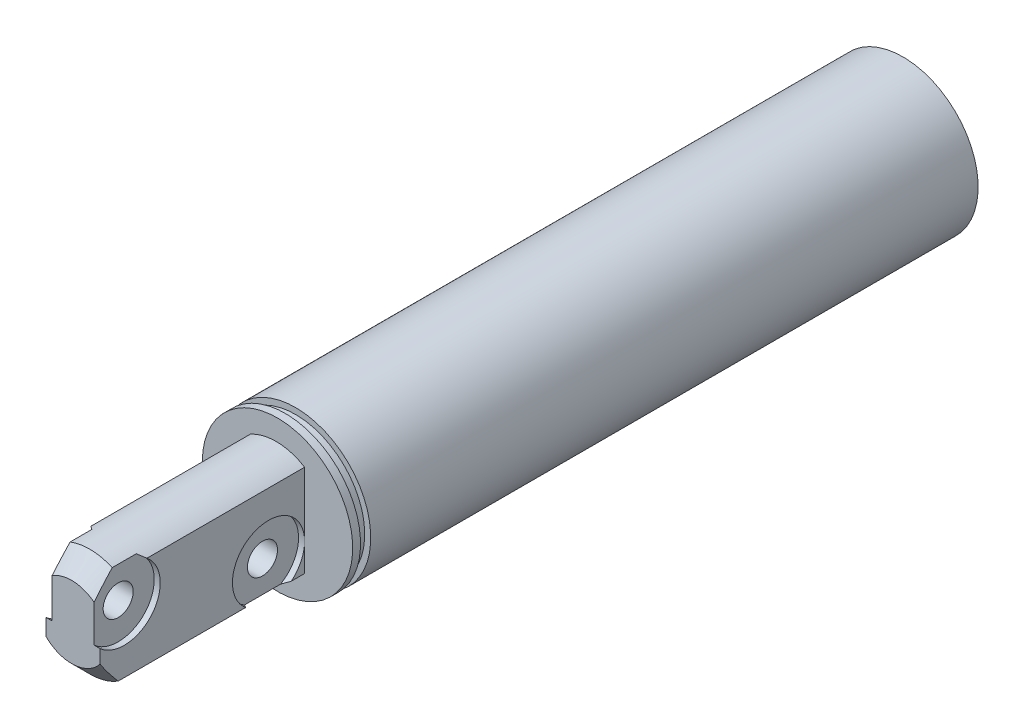
SolidWorks part; units mm, degrees
material "1060 合金"
ref_plane "前视基准面" through (0, 0, 0) normal (0, 0, 1) x (1, 0, 0)
ref_plane "上视基准面" through (0, 0, 0) normal (0, 1, 0) x (1, 0, 0)
ref_plane "右视基准面" through (0, 0, 0) normal (1, 0, 0) x (0, 0, -1)
sketch "草图1" plane through (0, 0, 0) normal (0, 0, 1) x (1, 0, 0)
  circle A0 centre (0, 0) radius 12.5
  dimension "D1" = 25
extrude "凸台-拉伸1" add sketch "草图1" along normal blind 104
sketch "草图6" plane through (0, 0, 0) normal (0, 1, 0) x (1, 0, 0)
  line L0 (0, 0) -> (0, -36.1312) construction
  line L1 (-12.5, 0) -> (-12.5, -104) construction
  line L2 (-12.5, -102.7) -> (-11.5, -102.7)
  line L3 (-12.5, -102.7) -> (-12.5, -101)
  line L4 (-12.5, -101) -> (-11.5, -101)
  line L5 (-11.5, -102.7) -> (-11.5, -101)
  line L6 (12.5, 0) -> (-12.5, 0) construction
  dimension "D1" = 1.7
  dimension "D2" = 101
  dimension "D3" = 1
revolve "切除-旋转1" cut sketch "草图6" angle 360 about L0
sketch "草图7" plane through (0, 0, 0) normal (0, 0, -1) x (-1, 0, 0)
  circle A0 centre (0, 0) radius 8
  circle A1 centre (0, 0) radius 12.5 construction
  dimension "D1" = 16
extrude "凸台-拉伸2" add sketch "草图7" along normal blind 2
hole_wizard "M8 螺纹孔1" positions "草图4" profile "草图5" tap size "M8" standard "GB"
sketch "草图4" plane through (0, 0, -2) normal (0, 0, -1) x (-1, 0, 0)
  point P0 (0, 0)
sketch "草图5" plane through (0, 0, -2) normal (1, 0, 0) x (0, 1, 0)
  line L0 (0, 0) -> (0, 84.2929)
  line L1 (0, 84.2929) -> (3.4, 82.25)
  line L2 (3.4, 82.25) -> (3.4, 0)
  line L5 (3.4, 0) -> (0, 0)
  line L10 (0, 84.2929) -> (-3.4, 82.25) construction
  line L11 (0, -6.35) -> (0, 107.95) construction
  dimension "螺纹孔钻头直径" = 6.8
  dimension "螺纹孔钻头深度" = 82.25
  dimension "导头角度" = 118
cosmetic thread "孔螺蚊线1" parameters "D1"=26, "D2"=8
sketch "草图9" plane through (0, 0, 104) normal (0, 0, 1) x (1, 0, 0)
  circle A0 centre (-0.2311, 0) radius 9
  dimension "D1" = 18
extrude "凸台-拉伸3" add sketch "草图9" along normal blind 34
sketch "草图8" plane through (0, 0, 0) normal (0, 1, 0) x (0, 0, -1)
  line L0 (0, 0) -> (-145.8395, 0) construction
  line L3 (-104, -14.9439) -> (-138, -4.5) construction
  line L4 (-104, 4.5) -> (-138, 4.5)
  line L5 (-104, 4.5) -> (-104, 14.9439)
  line L6 (-104, 14.9439) -> (-138, 14.9439)
  line L7 (-138, 4.5) -> (-138, 14.9439)
  line L8 (-104, 4.5) -> (-138, 14.9439) construction
  line L9 (-104, 14.9439) -> (-138, 4.5) construction
  line L11 (-104, -4.5) -> (-138, -14.9439) construction
  line L12 (-138, -4.5) -> (-138, -14.9439)
  line L13 (-104, -14.9439) -> (-138, -14.9439)
  line L14 (-104, -4.5) -> (-104, -14.9439)
  line L15 (-104, -4.5) -> (-138, -4.5)
  line L16 (-138, 9.2311) -> (-138, -8.7689) construction
  line L17 (-104, 12.5) -> (-104, -12.5) construction
  point P3 (-121, 9.722)
  point P18 (-121, -9.722)
  dimension "D1" = 9
extrude "切除-拉伸1" cut sketch "草图8" against normal through all both and the other way through all
sketch "草图10" plane through (4.5, 0, 0) normal (1, 0, 0) x (0, 0, -1)
  line L0 (-138, 7.6562) -> (-138, -7.6562) construction
  circle A0 centre (-134, 0) radius 2.5
  circle A1 centre (-110, 0) radius 2.5
  dimension "D2" = 5
  dimension "D3" = 19
  dimension "D1" = 4
extrude "切除-拉伸2" [suppressed] cut sketch "草图10" against normal through all
chamfer "倒角1" distance 3 angle 45 2 edges at (0.0358, -8.996, 138) (0.0358, 8.996, 138)
hole_wizard "Ø5.0 (5) 直径孔1" positions "草图12" profile "草图11" hole size "Ø5.0" standard "GB" end condition up to next
sketch "草图12" plane through (4.5, 0, 0) normal (1, 0, 0) x (0, 0, -1)
  line L0 (-138, 0) -> (-106.462, 0) construction
  line L1 (-138, 3.6901) -> (-138, -3.6901) construction
  point P0 (-110, -3)
  point P2 (-134, 3)
  dimension "D1" = 3
  dimension "D2" = 3
  dimension "D3" = 24
  dimension "D4" = 4
sketch "草图11" plane through (4.5, -3, 110) normal (0, 1, 0) x (0, 0, -1)
  line L0 (0, 0) -> (0, 9)
  line L1 (0, 9) -> (2.5, 9)
  line L2 (2.5, 9) -> (2.5, 0)
  line L5 (2.5, 0) -> (0, 0)
  line L11 (0, -6.35) -> (0, 107.95) construction
  dimension "通孔孔直径" = 5
  dimension "通孔孔深度" = 9
sketch "草图13" plane through (4.5, 0, 0) normal (1, 0, 0) x (0, 0, -1)
  circle A0 centre (-134, 3) radius 6
  circle A1 centre (-110, -3) radius 6
  dimension "D1" = 12
extrude "切除-拉伸3" cut sketch "草图13" against normal blind 1
mirror "镜向1" about plane through (0, 0, 0) normal (1, 0, 0) of "切除-拉伸3"
